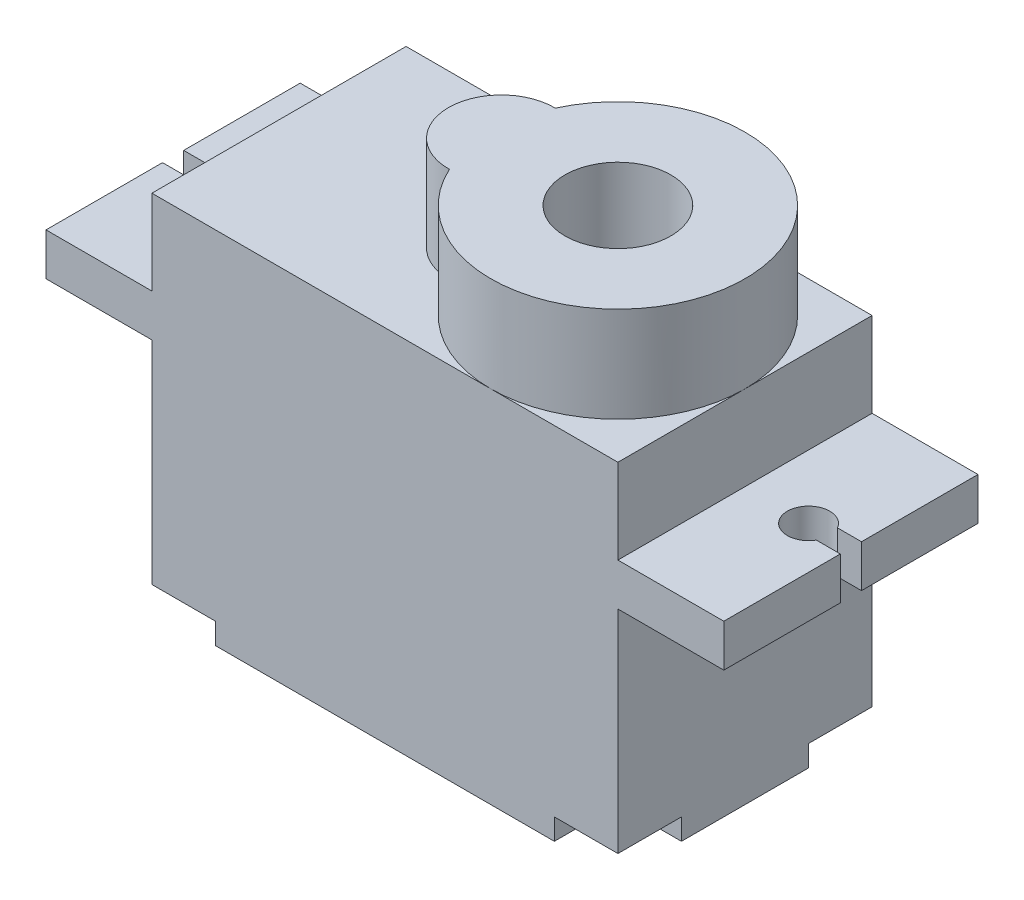
SolidWorks part; units mm, degrees
material "Plástico personalizado"
ref_plane "Alzado" through (0, 0, 0) normal (0, 0, 1) x (1, 0, 0)
ref_plane "Planta" through (0, 0, 0) normal (0, 1, 0) x (1, 0, 0)
ref_plane "Vista lateral" through (0, 0, 0) normal (1, 0, 0) x (0, 0, -1)
sketch "Croquis1" plane through (0, 0, 0) normal (0, 1, 0) x (1, 0, 0)
  line L1 (11, -6) -> (-11, -6)
  line L2 (11, -6) -> (11, 6)
  line L3 (11, 6) -> (-11, 6)
  line L4 (-11, -6) -> (-11, 6)
  line L5 (11, -6) -> (-11, 6) construction
  line L6 (11, 6) -> (-11, -6) construction
  point P0 (0, 0)
  dimension "D1" = 22
  dimension "D2" = 12
extrude "Saliente-Extruir1" add sketch "Croquis1" along normal blind 11
sketch "Croquis3" plane through (0, 11, 0) normal (0, 1, 0) x (1, 0, 0)
  line L0 (-11, 6) -> (-11, -6) construction
  line L1 (-6, 6) -> (-16, 6)
  line L2 (-6, 6) -> (-6, -6)
  line L3 (-6, -6) -> (-16, -6)
  line L4 (-16, 6) -> (-16, -6)
  line L5 (-6, 6) -> (-16, -6) construction
  line L6 (-6, -6) -> (-16, 6) construction
  line L7 (11, -6) -> (11, 6) construction
  line L8 (6, -6) -> (16, -6)
  line L9 (6, -6) -> (6, 6)
  line L10 (6, 6) -> (16, 6)
  line L11 (16, -6) -> (16, 6)
  line L12 (6, -6) -> (16, 6) construction
  line L13 (6, 6) -> (16, -6) construction
  point P0 (-11, 0)
  point P7 (11, 0)
  dimension "D1" = 10
  dimension "D2" = 10
extrude "Saliente-Extruir2" add sketch "Croquis3" along normal blind 2
sketch "Croquis4" plane through (0, 11, 0) normal (0, 1, 0) x (1, 0, 0)
  line L1 (6, -6) -> (-6, -6)
  line L2 (6, -6) -> (6, 6)
  line L3 (6, 6) -> (-6, 6)
  line L4 (-6, -6) -> (-6, 6)
  line L5 (6, -6) -> (-6, 6) construction
  line L6 (6, 6) -> (-6, -6) construction
  point P0 (0, 0)
extrude "Saliente-Extruir3" add sketch "Croquis4" along normal blind 6
sketch "Croquis5" plane through (0, 13, 0) normal (0, 1, 0) x (1, 0, 0)
  line L0 (-16, 0) -> (-16, 0.5)
  line L1 (-16, 6) -> (-16, -6) construction
  line L2 (-16, 0) -> (-16, -0.5)
  line L3 (-16, 0) -> (-15, 0)
  line L4 (-16, 0.5) -> (-15, 0.5)
  line L5 (-16, -0.5) -> (-15.9117, -0.5)
  line L7 (-15.9117, -0.5) -> (-15, -0.5)
  line L9 (-15, 0.5) -> (-14.866, 0.5)
  line L10 (-15, -0.5) -> (-14.866, -0.5)
  arc A0 (-14.866, -0.5) -> (-14.866, 0.5) centre (-14, 0) ccw
  line M5 (-16, 6) -> (-16, -6)
  dimension "D1" = 0.5
  dimension "D2" = 0.5
  dimension "D3" = 1
  dimension "D4" = 1
extrude "Cortar-Extruir1" cut sketch "Croquis5" against normal blind 2 contours L10 A0 L9 L4 L5 L7 M5 region at (-14.3684, 13, 0)
sketch "Croquis6" plane through (0, 13, 0) normal (0, 1, 0) x (1, 0, 0)
  line L0 (6, -6) -> (16, -6) construction
  line L1 (-6, 6) -> (-11, 6)
  line L2 (-6, 6) -> (-6, -6)
  line L3 (-6, -6) -> (-11, -6)
  line L4 (-11, 6) -> (-11, -6)
  line L5 (6, 6) -> (11, 6)
  line L6 (6, 6) -> (6, -6)
  line L7 (6, -6) -> (11, -6)
  line L8 (11, 6) -> (11, -6)
extrude "Saliente-Extruir4" add sketch "Croquis6" along normal blind 4
sketch "Croquis7" plane through (0, 13, 0) normal (0, 1, 0) x (1, 0, 0)
  line L1 (16, -6) -> (16, 6) construction
  line L2 (16, 0) -> (16, 0.5)
  line L3 (16, 0) -> (16, -0.5)
  line L5 (16, 0.5) -> (14.907, 0.5)
  line L6 (16, -0.5) -> (15, -0.5)
  line L7 (15, -0.5) -> (14.866, -0.5)
  line L8 (14.907, 0.5) -> (14.866, 0.5)
  arc A0 (14.866, 0.5) -> (14.866, -0.5) centre (14, 0) ccw
  dimension "D2" = 0.5
  dimension "D3" = 0.5
extrude "Cortar-Extruir2" cut sketch "Croquis7" against normal blind 4
sketch "Croquis8" plane through (0, 17, 0) normal (0, 1, 0) x (1, 0, 0)
  circle A0 centre (5, 0) radius 6
extrude "Saliente-Extruir5" add sketch "Croquis8" along normal blind 4.5
sketch "Croquis9" plane through (0, 17, 0) normal (0, 1, 0) x (1, 0, 0)
  line L0 (11, 0) -> (-0.5, 0)
  line L1 (11, -6) -> (11, 6) construction
  circle A0 centre (-0.5, 0) radius 2.5
  arc M2 (5, -6) -> (5, 6) centre (5, 0) cw
  dimension "D2" = 5
  dimension "D1" = 11.5
extrude "Saliente-Extruir6" add sketch "Croquis9" along normal up to surface (4.5 mm away) contours A0 M2 region at (-1.7294, 17, 0) up to face at (5, 21.5, 6)
sketch "Croquis10" plane through (0, 0, 0) normal (0, -1, 0) x (-1, 0, 0)
  line L0 (11, -6) -> (11, -3)
  line L1 (11, -6) -> (-11, -6) construction
  line L2 (11, 6) -> (11, -6) construction
  line L3 (11, -6) -> (8, -6)
  line L4 (8, -6) -> (8, -3)
  line L5 (8, -3) -> (11, -3)
  dimension "D1" = 3
  dimension "D2" = 3
extrude "Cortar-Extruir3" cut sketch "Croquis10" against normal blind 1
fillet "Redondeo1" radius 1.5 1 edges at (-8, 0.5, 3)
sketch "Croquis11" plane through (0, 0, 0) normal (0, -1, 0) x (-1, 0, 0)
  line L0 (11, 6) -> (8, 6)
  line L1 (-11, 6) -> (11, 6) construction
  line L2 (11, 6) -> (11, 3)
  line L3 (11, 6) -> (11, -3) construction
  line L4 (8, 6) -> (8, 3)
  line L5 (8, 3) -> (11, 3)
  line L6 (-11, -6) -> (-8, -6)
  line L7 (8, -6) -> (-11, -6) construction
  line L8 (-11, -6) -> (-11, -3)
  line L9 (-11, -6) -> (-11, 6) construction
  line L10 (-11, 6) -> (-8, 6)
  line L11 (-11, 6) -> (-11, 3)
  line L12 (-11, -3) -> (-8, -3)
  line L13 (-8, -3) -> (-8, -6)
  line L14 (-8, 6) -> (-8, 3)
  line L15 (-8, 3) -> (-11, 3)
  dimension "D1" = 3
  dimension "D2" = 3
  dimension "D3" = 3
  dimension "D4" = 3
  dimension "D5" = 3
  dimension "D6" = 3
extrude "Cortar-Extruir4" cut sketch "Croquis11" against normal blind 1
fillet "Redondeo3" radius 1.5 3 edges at (8, 0.5, 3) (8, 0.5, -3) (-8, 0.5, -3)
sketch "Croquis12" plane through (0, 1, 0) normal (0, -1, 0) x (-1, 0, 0)
  line L0 (8, -6) -> (11, -6) construction
  line L1 (11, -6) -> (11, -3) construction
  line L2 (11, 6) -> (8, 6) construction
  line L4 (-11, -3) -> (-11, -6) construction
  circle A0 centre (9.75, -4.75) radius 1
  circle A1 centre (9.75, 4.75) radius 1
  circle A2 centre (-9.75, -4.75) radius 1
  circle A3 centre (-9.75, 4.75) radius 1
  dimension "D5" = 2
  dimension "D6" = 2
  dimension "D7" = 2
  dimension "D8" = 2
  dimension "D1" = 1.25
  dimension "D2" = 1.25
  dimension "D3" = 1.25
  dimension "D4" = 1.25
extrude "Cortar-Extruir5" cut sketch "Croquis12" against normal blind 3
sketch "Croquis13" plane through (0, 21.5, 0) normal (0, 1, 0) x (1, 0, 0)
  circle A0 centre (5, 0) radius 2.5
  dimension "D1" = 5
extrude "Cortar-Extruir6" cut sketch "Croquis13" against normal blind 5
